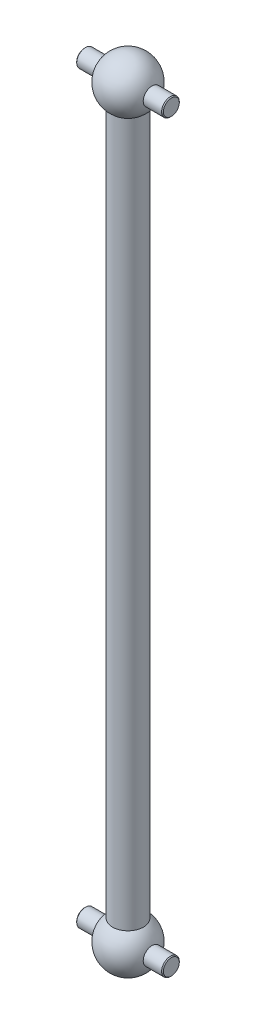
SolidWorks part; units mm, degrees
material "Acier inoxydable chromé"
ref_plane "Plan de face" through (0, 0, 0) normal (0, 0, 1) x (1, 0, 0)
ref_plane "Plan de dessus" through (0, 0, 0) normal (0, 1, 0) x (1, 0, 0)
ref_plane "Plan de droite" through (0, 0, 0) normal (1, 0, 0) x (0, 0, -1)
sketch "Esquisse1" plane through (0, 0, 0) normal (0, 0, 1) x (1, 0, 0)
  line L0 (0, 63.1434) -> (0, -66.5336) construction
  line L1 (-11.0193, 0) -> (8.9419, 0) construction
  line L2 (-1.75, -39.7875) -> (-1.75, 39.7875)
  line L3 (0, 45) -> (0, -45)
  arc A0 (0, 45) -> (-1.75, 39.7875) centre (0, 42.1) ccw
  arc A1 (0, -45) -> (-1.75, -39.7875) centre (0, -42.1) cw
  point P12 (-1.75, 0)
  point P13 (0, 42.1)
  dimension "D1" = 2.9
  dimension "D2" = 3.5
  dimension "D3" = 90
revolve "Révolution1" add sketch "Esquisse1" angle 360 about L3
sketch "Esquisse2" plane through (0, 0, 0) normal (1, 0, 0) x (0, 0, -1)
  circle A0 centre (0, 42.1) radius 1
  dimension "D1" = 2
extrude "Boss.-Extru.1" add sketch "Esquisse2" along normal blind 4.9 and the other way blind 4.9
mirror "Symétrie3" about plane through (0, 0, 0) normal (0, 1, 0) of "Boss.-Extru.1"
chamfer "Chanfrein1" distance 0.1 angle 45 4 edges at (4.9, 42.1, -1) (-4.9, 42.1, -1) (4.9, -42.1, -1) (-4.9, -42.1, -1)
